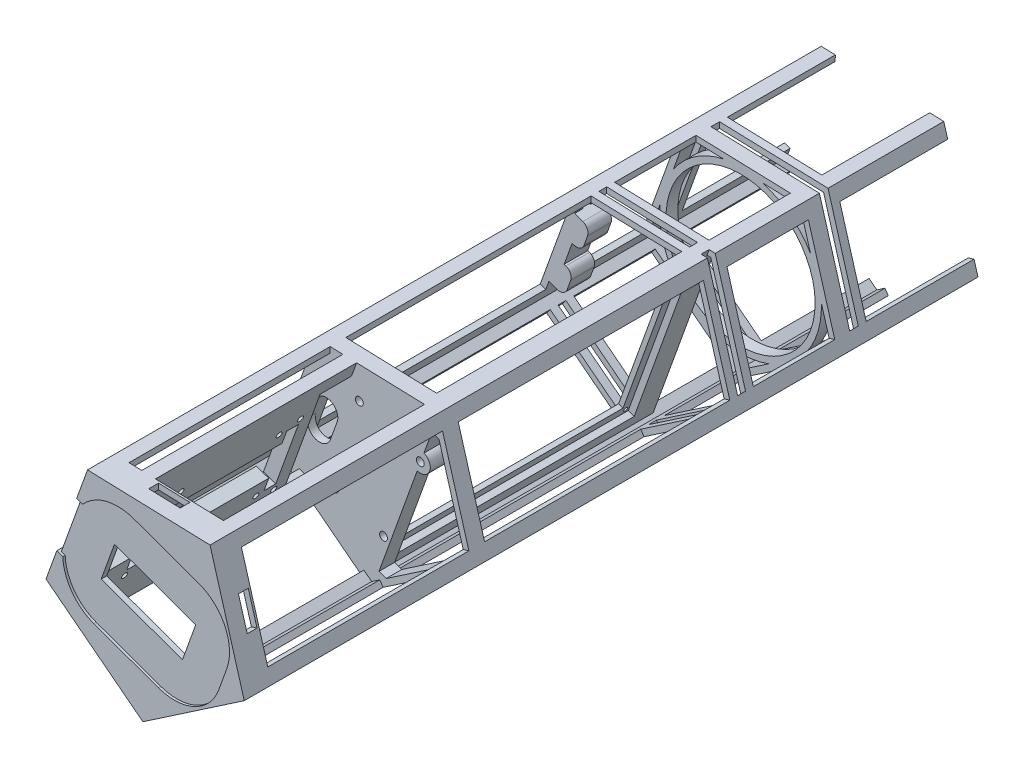
SolidWorks part; units mm, degrees
ref_plane "Front Plane" through (0, 0, 0) normal (0, 0, 1) x (1, 0, 0)
ref_plane "Top Plane" through (0, 0, 0) normal (0, 1, 0) x (1, 0, 0)
ref_plane "Right Plane" through (0, 0, 0) normal (1, 0, 0) x (0, 0, -1)
sketch "Sketch3" plane through (0, 0, 0) normal (0, 0, 1) x (1, 0, 0)
  line L0 (0, 0) -> (16.2851, 21.0012) construction
  line L1 (15.1489, 19.536) -> (-13.8986, 20.4445)
  line L2 (-13.8986, 20.4445) -> (-23.7387, -6.9006)
  line L3 (-23.7387, -6.9006) -> (-0.7728, -24.7093)
  line L4 (-0.7728, -24.7093) -> (23.2611, -8.3705)
  line L5 (0, 0) -> (29.9163, 0) construction
  line L6 (0, 0) -> (25.0057, -8.9983) construction
  line L10 (-0.8307, -26.5625) -> (25.0057, -8.9983)
  line L11 (25.0057, -8.9983) -> (16.2851, 21.0012)
  line L12 (16.2851, 21.0012) -> (-14.941, 21.9778)
  line L13 (-14.941, 21.9778) -> (-25.5191, -7.4182)
  line L14 (-25.5191, -7.4182) -> (-0.8307, -26.5625)
  line L15 (23.2611, -8.3705) -> (15.1489, 19.536)
  circle A0 centre (0, 0) radius 20 construction
  point P4 (0, 0)
  point P14 (0, 0)
  dimension "D2" = 40
extrude "Boss-Extrude2" add sketch "Sketch3" along normal blind 185
ref_plane "Plane1" through (0, 0, 92.5) normal (0, 0, 1) x (1, 0, 0)
sketch "Sketch4" plane through (0, 0, 0) normal (0, 0, -1) x (-1, 0, 0)
  line L0 (14.745, 18.0921) -> (16.1564, 18.6)
  line L1 (13.8986, 20.4445) -> (23.7387, -6.9006) construction
  line L2 (14.941, 21.9778) -> (25.5191, -7.4182) construction
  line L3 (24.3036, -4.0404) -> (22.8922, -4.5483)
  line L4 (22.8922, -4.5483) -> (14.745, 18.0921)
  line L5 (24.3036, -4.0404) -> (16.1564, 18.6)
  dimension "D1" = 2.5
  dimension "D2" = 2.5
extrude "Cut-Extrude1" cut sketch "Sketch4" against normal offset from surface (180 mm away) 5 up to face at (0, 0, 185)
ref_point "Point1"
ref_axis "Axis1" through (0, 0, 185) along (0, 0, 1)
pattern_circular "CirPattern1" count 5 over 360 about axis through (0, 0, 185) along (0, 0, 1) of "Cut-Extrude1"
ref_plane "Plane2" through (0, 0, 92.5) normal (0, 0, 1) x (1, 0, 0)
sketch "Sketch5" plane through (0, 0, 92.5) normal (0, 0, 1) x (1, 0, 0)
  line L0 (-2.0696, -25.6018) -> (14.7182, 21.0502) construction
  line L2 (-24.1133, -8.5083) -> (-1.8275, -25.7895) construction
  line L3 (23.2611, -8.3705) -> (0, 0) construction
  line L4 (-4.3961, -23.7977) -> (11.7756, 21.1422)
  line L8 (-2.0696, -25.6018) -> (-4.3961, -23.7977)
  line L10 (14.7182, 21.0502) -> (11.7756, 21.1422)
  line L11 (-2.0696, -25.6018) -> (14.7182, 21.0502)
  line L12 (-22.8004, 22.2236) -> (6.2471, 21.3151) construction
  dimension "D1" = 18
  dimension "D2" = 2.8
extrude "Boss-Extrude3" add sketch "Sketch5" along normal mid plane 64.5
sketch "Sketch6" plane through (0, 0, 124.75) normal (0, 0, 1) x (1, 0, 0)
  line L5 (-25.5191, -7.4182) -> (-0.8307, -26.5625)
  line L6 (-0.8307, -26.5625) -> (25.0057, -8.9983)
  line L7 (25.0057, -8.9983) -> (16.2851, 21.0012)
  line L8 (16.2851, 21.0012) -> (-14.941, 21.9778)
  line L9 (-14.941, 21.9778) -> (-25.5191, -7.4182)
  line L10 (-25.5191, -7.4182) -> (-0.8307, -26.5625)
  line L11 (-0.8307, -26.5625) -> (25.0057, -8.9983)
  line L12 (25.0057, -8.9983) -> (16.2851, 21.0012)
  line L13 (16.2851, 21.0012) -> (-14.941, 21.9778)
  line L14 (-14.941, 21.9778) -> (-25.5191, -7.4182)
  dimension "D1" = 0
extrude "Boss-Extrude4" add sketch "Sketch6" along normal blind 4
sketch "Sketch7" plane through (0, 0, 124.75) normal (0, 0, -1) x (-1, 0, 0)
  line L0 (-3.6897, -1.3278) -> (20.23, 7.2798) construction
  line L1 (-11.7756, 21.1422) -> (4.3961, -23.7977) construction
  line L2 (16.1564, 18.6) -> (24.3036, -4.0404) construction
  line L4 (19.0326, -2.4504) -> (13.1071, 14.0159)
  line L5 (0.2139, -9.2223) -> (-5.7115, 7.244)
  line L7 (19.0326, -2.4504) -> (-5.7115, 7.244) construction
  line L8 (0.2139, -9.2223) -> (13.1071, 14.0159) construction
  line L9 (9.6232, -5.8364) -> (3.6978, 10.63) construction
  line L11 (-11.7756, 21.1422) -> (4.3961, -23.7977) construction
  arc A0 (-5.7115, 7.244) -> (13.1071, 14.0159) centre (3.6978, 10.63) cw
  arc A1 (0.2139, -9.2223) -> (19.0326, -2.4504) centre (9.6232, -5.8364) ccw
  point P7 (6.6605, 2.3968)
  point P9 (13.0092, -15.2457)
  point P14 (0.3119, 20.0393)
  point P15 (0, 0)
  point P16 (7.1485, 2.5724)
  point P17 (7.4662, 2.6867)
  dimension "D1" = 37.5
  dimension "D2" = 20
  dimension "D3" = 1
extrude "Cut-Extrude2" cut sketch "Sketch7" against normal blind 2
sketch "Sketch8" plane through (6.3243, -2.2758, 0) normal (0.9409, -0.3386, 0) x (0, 0, -1)
  line L0 (-60.25, 0) -> (-124.75, 0) construction
  line L1 (-124.75, -23.2131) -> (-124.75, 23.2131) construction
  line L3 (-60.25, -23.2131) -> (-60.25, 23.2131) construction
  line L5 (-123, -20.5) -> (-123, 20.5)
  line L6 (-123, -20.5) -> (-62, -20.5)
  line L7 (-123, 20.5) -> (-62, 20.5)
  line L8 (-62, -20.5) -> (-62, 20.5)
  line L14 (-62, 20.5) -> (-123, -20.5) construction
  line L15 (-62, -20.5) -> (-123, 20.5) construction
  point P2 (0, 0)
  point P5 (0, 0)
  point P6 (0, 0)
  point P11 (-92.5, 0)
  point P14 (-92.5, 0)
  dimension "D1" = 61
  dimension "D2" = 41
extrude "Cut-Extrude3" cut sketch "Sketch8" against normal blind 1.6
sketch "Sketch9" plane through (4.8189, -1.7341, 0) normal (0.9409, -0.3386, 0) x (0, 0, -1)
  line L8 (-121, -18.5) -> (-64, -18.5)
  line L9 (-64, -18.5) -> (-64, 18.5)
  line L10 (-64, 18.5) -> (-121, 18.5)
  line L11 (-121, 18.5) -> (-121, -18.5)
  line L12 (-121, -18.5) -> (-64, -18.5)
  line L13 (-64, -18.5) -> (-64, 18.5)
  line L14 (-64, 18.5) -> (-121, 18.5)
  line L15 (-121, 18.5) -> (-121, -18.5)
  dimension "D1" = 2
extrude "Cut-Extrude4" cut sketch "Sketch9" against normal up to surface (1.2 mm away) up to face at (3.6897, -1.3278, 92.5)
sketch "Sketch10" plane through (0, 0, 60.25) normal (0, 0, -1) x (-1, 0, 0)
  line L25 (-23.2611, -8.3705) -> (0.7728, -24.7093)
  line L26 (0.7728, -24.7093) -> (23.7387, -6.9006)
  line L27 (23.7387, -6.9006) -> (13.8986, 20.4445)
  line L28 (13.8986, 20.4445) -> (-15.1489, 19.536)
  line L29 (-15.1489, 19.536) -> (-23.2611, -8.3705)
  line L30 (0.8307, -26.5625) -> (25.5191, -7.4182)
  line L31 (-25.0057, -8.9983) -> (0.8307, -26.5625)
  line L32 (-16.2851, 21.0012) -> (-25.0057, -8.9983)
  line L33 (14.941, 21.9778) -> (-16.2851, 21.0012)
  line L34 (25.5191, -7.4182) -> (14.941, 21.9778)
  line L40 (0.8307, -26.5625) -> (25.5191, -7.4182)
  line L41 (-25.0057, -8.9983) -> (0.8307, -26.5625)
  line L42 (-16.2851, 21.0012) -> (-25.0057, -8.9983)
  line L43 (14.941, 21.9778) -> (-16.2851, 21.0012)
  line L44 (25.5191, -7.4182) -> (14.941, 21.9778)
  point P8 (0, 0)
  point P11 (-0.8687, -22.1155)
  dimension "D1" = 0
extrude "Boss-Extrude5" add sketch "Sketch10" against normal blind 2
sketch "Sketch11" plane through (0, 0, 60.25) normal (0, 0, -1) x (-1, 0, 0)
  line L0 (3.8621, -22.3137) -> (4.3961, -23.7977)
  line L1 (4.3961, -23.7977) -> (3.6676, -24.3627)
  line L2 (-11.2416, 19.6582) -> (-11.7756, 21.1422)
  line L3 (-11.7756, 21.1422) -> (-12.697, 21.1134)
  line L4 (21.7631, -8.4326) -> (3.8621, -22.3137)
  line L7 (3.8621, -22.3137) -> (-11.2416, 19.6582)
  line L9 (-14.1842, 19.5662) -> (1.5355, -24.1178)
  line L10 (-14.1842, 19.5662) -> (1.5355, -24.1178)
  line L11 (-12.697, 21.1134) -> (11.3529, 21.8656) construction
  line L13 (3.8621, -22.3137) -> (-11.2416, 19.6582) construction
  line L18 (22.6823, -9.618) -> (3.6676, -24.3627) construction
  line L19 (3.8621, -22.3137) -> (-11.2416, 19.6582)
  line L27 (-11.2416, 19.6582) -> (11.3998, 20.3663)
  line L31 (1.5355, -24.1178) -> (2.7484, -23.1773)
  line L33 (1.5355, -24.1178) -> (2.7484, -23.1773)
  line L35 (2.7484, -23.1773) -> (3.6676, -24.3627)
  line L37 (2.7484, -23.1773) -> (3.6676, -24.3627)
  line L39 (3.6676, -24.3627) -> (22.6823, -9.618)
  line L41 (22.6823, -9.618) -> (21.7631, -8.4326)
  line L43 (11.3998, 20.3663) -> (11.3529, 21.8656)
  line L45 (11.3529, 21.8656) -> (-12.697, 21.1134)
  line L47 (-12.697, 21.1134) -> (-12.6502, 19.6141)
  line L48 (-12.697, 21.1134) -> (-12.6502, 19.6141)
  line L49 (-12.6502, 19.6141) -> (-14.1842, 19.5662)
  line L50 (-12.6502, 19.6141) -> (-14.1842, 19.5662)
  dimension "D1" = 0
extrude "Boss-Extrude6" add sketch "Sketch11" along normal blind 4
sketch "Sketch12" plane through (0, 0, 56.25) normal (0, 0, -1) x (-1, 0, 0)
  line L0 (0.7728, -24.7093) -> (23.7387, -6.9006)
  line L1 (23.7387, -6.9006) -> (13.8986, 20.4445)
  line L2 (13.8986, 20.4445) -> (-15.1489, 19.536)
  line L3 (-15.1489, 19.536) -> (-23.2611, -8.3705)
  line L4 (-23.2611, -8.3705) -> (0.7728, -24.7093)
  line L5 (0.8307, -26.5625) -> (25.5191, -7.4182)
  line L6 (-25.0057, -8.9983) -> (0.8307, -26.5625)
  line L7 (-16.2851, 21.0012) -> (-25.0057, -8.9983)
  line L8 (14.941, 21.9778) -> (-16.2851, 21.0012)
  line L9 (25.5191, -7.4182) -> (14.941, 21.9778)
  line L10 (0.8307, -26.5625) -> (25.5191, -7.4182)
  line L11 (-25.0057, -8.9983) -> (0.8307, -26.5625)
  line L12 (-16.2851, 21.0012) -> (-25.0057, -8.9983)
  line L13 (14.941, 21.9778) -> (-16.2851, 21.0012)
  line L14 (25.5191, -7.4182) -> (14.941, 21.9778)
  point P15 (0, -21.7043)
  dimension "D1" = 0
extrude "Boss-Extrude7" add sketch "Sketch12" against normal blind 2
ref_plane "Plane3" through (0, 0, 32.5) normal (0, 0, 1) x (1, 0, 0)
sketch "Sketch14" plane through (0, 0, 32.5) normal (0, 0, 1) x (1, 0, 0)
  line L5 (-25.5191, -7.4182) -> (-0.8307, -26.5625)
  line L6 (-0.8307, -26.5625) -> (25.0057, -8.9983)
  line L7 (25.0057, -8.9983) -> (16.2851, 21.0012)
  line L8 (16.2851, 21.0012) -> (-14.941, 21.9778)
  line L9 (-14.941, 21.9778) -> (-25.5191, -7.4182)
  line L11 (-0.8307, -26.5625) -> (25.0057, -8.9983)
  line L12 (25.0057, -8.9983) -> (16.2851, 21.0012)
  line L16 (23.2611, -8.3705) -> (15.3259, -13.7651)
  line L18 (-0.7728, -24.7093) -> (-8.3554, -18.8294)
  line L20 (-23.7387, -6.9006) -> (-20.4898, 2.1279)
  line L22 (-13.8986, 20.4445) -> (-4.308, 20.1445)
  line L24 (15.1489, 19.536) -> (17.8273, 10.3221)
  line L25 (7.1625, -19.3147) -> (-0.7728, -24.7093)
  line L26 (20.5827, 0.8433) -> (23.2611, -8.3705)
  line L27 (5.5584, 19.8359) -> (15.1489, 19.536)
  line L28 (-17.1475, 11.416) -> (-13.8986, 20.4445)
  line L29 (-16.1561, -12.7805) -> (-23.7387, -6.9006)
  line L30 (16.2851, 21.0012) -> (-14.941, 21.9778)
  line L31 (-14.941, 21.9778) -> (-25.5191, -7.4182)
  line L32 (-25.5191, -7.4182) -> (-0.8307, -26.5625)
  circle A3 centre (0, 0) radius 19
  arc A8 (15.3259, -13.7651) -> (20.5827, 0.8433) centre (0, 0) ccw
  circle A9 centre (0, 0) radius 20.6 construction
  arc A10 (17.8273, 10.3221) -> (5.5584, 19.8359) centre (0, 0) ccw
  arc A11 (-4.308, 20.1445) -> (-17.1475, 11.416) centre (0, 0) ccw
  arc A12 (-20.4898, 2.1279) -> (-16.1561, -12.7805) centre (0, 0) ccw
  arc A13 (-8.3554, -18.8294) -> (7.1625, -19.3147) centre (0, 0) ccw
  dimension "D2" = 38
  dimension "D1" = 0
  dimension "D3" = 1.6
extrude "Boss-Extrude8" add sketch "Sketch14" along normal blind 3
ref_plane "Plane4" through (0, 0, 29.5) normal (0, 0, -1) x (-1, 0, 0)
sketch "Sketch15" plane through (0, 0, 29.5) normal (0, 0, -1) x (-1, 0, 0)
  line L0 (-23.2611, -8.3705) -> (0.7728, -24.7093)
  line L1 (0.7728, -24.7093) -> (23.7387, -6.9006)
  line L2 (23.7387, -6.9006) -> (13.8986, 20.4445)
  line L3 (13.8986, 20.4445) -> (-15.1489, 19.536)
  line L4 (-15.1489, 19.536) -> (-23.2611, -8.3705)
  line L5 (0.8307, -26.5625) -> (25.5191, -7.4182)
  line L6 (-25.0057, -8.9983) -> (0.8307, -26.5625)
  line L7 (-16.2851, 21.0012) -> (-25.0057, -8.9983)
  line L8 (14.941, 21.9778) -> (-16.2851, 21.0012)
  line L9 (25.5191, -7.4182) -> (14.941, 21.9778)
  line L10 (0.8307, -26.5625) -> (25.5191, -7.4182)
  line L11 (-25.0057, -8.9983) -> (0.8307, -26.5625)
  line L12 (-16.2851, 21.0012) -> (-25.0057, -8.9983)
  line L13 (14.941, 21.9778) -> (-16.2851, 21.0012)
  line L14 (25.5191, -7.4182) -> (14.941, 21.9778)
  point P15 (-13.7443, 17.3013)
  point P16 (-15.1489, 19.536)
  dimension "D1" = 0
extrude "Boss-Extrude9" add sketch "Sketch15" along normal blind 2
sketch "Sketch18" plane through (0, 0, 32.5) normal (0, 0, -1) x (-1, 0, 0)
  line L0 (22.8922, -4.5483) -> (24.3036, -4.0404)
  line L1 (24.3036, -4.0404) -> (16.1564, 18.6)
  line L2 (16.1564, 18.6) -> (14.745, 18.0921)
  line L3 (14.745, 18.0921) -> (22.8922, -4.5483)
  line L4 (11.3998, 20.3663) -> (11.3529, 21.8656)
  line L5 (11.3529, 21.8656) -> (-12.697, 21.1134)
  line L6 (-12.697, 21.1134) -> (-12.6502, 19.6141)
  line L7 (-12.6502, 19.6141) -> (11.3998, 20.3663)
  line L8 (-15.8468, 17.1354) -> (-17.2872, 17.5541)
  line L9 (-17.2872, 17.5541) -> (-24.0037, -5.5512)
  line L10 (-24.0037, -5.5512) -> (-22.5633, -5.9699)
  line L11 (-22.5633, -5.9699) -> (-15.8468, 17.1354)
  line L12 (-21.1936, -9.7761) -> (-22.0369, -11.0166)
  line L13 (-22.0369, -11.0166) -> (-2.138, -24.5443)
  line L14 (-2.138, -24.5443) -> (-1.2947, -23.3038)
  line L15 (-1.2947, -23.3038) -> (-21.1936, -9.7761)
  line L16 (3.6676, -24.3627) -> (22.6823, -9.618)
  line L17 (22.6823, -9.618) -> (21.7631, -8.4326)
  line L18 (21.7631, -8.4326) -> (2.7484, -23.1773)
  line L19 (2.7484, -23.1773) -> (3.6676, -24.3627)
extrude "Boss-Extrude10" add sketch "Sketch18" along normal blind 0.8
sketch "Sketch25" plane through (0, 0, 56.25) normal (0, 0, -1) x (-1, 0, 0)
  line L0 (23.5979, -4.2944) -> (15.4507, 18.3461) construction
  line L1 (15.0407, 12.1611) -> (19.3409, 0.2112) construction
  line L2 (16.24, 16.1529) -> (11.5729, 14.4735)
  line L3 (24.3036, -4.0404) -> (22.8922, -4.5483) construction
  line L8 (14.745, 18.0921) -> (16.1564, 18.6) construction
  line L9 (22.5345, -1.339) -> (16.5142, 15.3907) construction
  line L10 (22.5345, -1.339) -> (4.6097, -7.7893) construction
  line L11 (16.5142, 15.3907) -> (-1.4105, 8.9405) construction
  line L12 (4.6097, -7.7893) -> (-1.4105, 8.9405) construction
  line L13 (19.5243, 7.0259) -> (0, 0) construction
  line L14 (16.24, 16.1529) -> (18.5086, 9.8487) construction
  line L15 (11.5729, 14.4735) -> (13.8415, 8.1692)
  line L16 (16.175, 9.0089) -> (13.8415, 8.1692)
  line L17 (13.9065, 15.3132) -> (16.175, 9.0089) construction
  line L18 (17.3743, 13.0008) -> (12.7072, 11.3213) construction
  line L19 (21.6744, 1.0509) -> (17.0074, -0.6285) construction
  line L20 (20.4752, -2.9409) -> (18.2066, 3.3633) construction
  line L21 (18.2066, 3.3633) -> (15.8731, 2.5236)
  line L22 (18.1417, -3.7806) -> (15.8731, 2.5236)
  line L23 (22.8087, -2.1012) -> (20.5401, 4.2031) construction
  line L24 (22.8087, -2.1012) -> (18.1417, -3.7806)
  line L25 (18.5086, 9.8487) -> (20.5401, 4.2031) construction
  line L28 (16.175, 9.0089) -> (18.2066, 3.3633)
  line L29 (16.24, 16.1529) -> (16.9457, 16.4068)
  line L30 (24.3036, -4.0404) -> (16.1564, 18.6) construction
  line L31 (16.9457, 16.4068) -> (23.5144, -1.8472)
  line L32 (23.5144, -1.8472) -> (22.8087, -2.1012)
  circle A0 centre (15.0407, 12.1611) radius 1 construction
  circle A1 centre (19.3409, 0.2112) radius 1 construction
  circle A2 centre (19.3409, 0.2112) radius 1 construction
  point P17 (17.1908, 6.1861)
  dimension "D3" = 2
  dimension "D4" = 12.7
  dimension "D1" = 17.78
  dimension "D2" = 19.05
  dimension "D5" = 16.57
  dimension "D6" = 6
sketch "Sketch26" plane through (0, 0, 56.25) normal (0, 0, -1) x (-1, 0, 0)
  circle A0 centre (19.3409, 0.2112) radius 1 construction
  circle A1 centre (19.3409, 0.2112) radius 1
  circle A2 centre (15.0407, 12.1611) radius 1 construction
  circle A3 centre (15.0407, 12.1611) radius 1
sketch "Sketch28" plane through (0, 0, 56.25) normal (0, 0, -1) x (-1, 0, 0)
  line L0 (23.5979, -4.2944) -> (15.4507, 18.3461) construction
  line L1 (22.5345, -1.339) -> (4.6097, -7.7893) construction
  line L2 (4.6097, -7.7893) -> (-1.4105, 8.9405) construction
  line L3 (16.5142, 15.3907) -> (-1.4105, 8.9405) construction
  line L4 (22.5345, -1.339) -> (16.5142, 15.3907) construction
  line L5 (22.5345, -1.339) -> (4.6097, -7.7893) construction
  line L6 (4.6097, -7.7893) -> (-1.4105, 8.9405) construction
  line L7 (16.5142, 15.3907) -> (-1.4105, 8.9405) construction
  line L8 (22.7904, -1.4595) -> (16.6347, 15.6466)
  line L9 (16.6347, 15.6466) -> (-1.6664, 9.061)
  line L10 (4.4892, -8.0452) -> (-1.6664, 9.061)
  line L11 (22.7904, -1.4595) -> (4.4892, -8.0452)
  dimension "D1" = 0.2
extrude "Boss-Extrude12" add sketch "Sketch25" against normal up to surface (6 mm away) up to face at (-19.5243, 7.0259, 62.25)
extrude "Cut-Extrude6" cut sketch "Sketch26" against normal blind 5
fillet "Fillet1" radius 2 4 edges at (-18.1417, -3.7806, 59.25) (-15.8731, 2.5236, 59.25) (-13.8415, 8.1692, 59.25) (-11.5729, 14.4735, 59.25)
sketch "Sketch29" plane through (0, 0, 185) normal (0, 0, 1) x (1, 0, 0)
  line L5 (-25.5191, -7.4182) -> (-0.8307, -26.5625)
  line L6 (-0.8307, -26.5625) -> (25.0057, -8.9983)
  line L7 (25.0057, -8.9983) -> (16.2851, 21.0012)
  line L8 (16.2851, 21.0012) -> (-14.941, 21.9778)
  line L9 (-14.941, 21.9778) -> (-25.5191, -7.4182)
  line L10 (-25.5191, -7.4182) -> (-0.8307, -26.5625)
  line L11 (-0.8307, -26.5625) -> (25.0057, -8.9983)
  line L12 (25.0057, -8.9983) -> (16.2851, 21.0012)
  line L13 (16.2851, 21.0012) -> (-14.941, 21.9778)
  line L14 (-14.941, 21.9778) -> (-25.5191, -7.4182)
  dimension "D1" = 0
extrude "Boss-Extrude13" add sketch "Sketch29" along normal blind 2
sketch "Sketch30" plane through (0, 0, 187) normal (0, 0, 1) x (1, 0, 0)
  line L0 (25.0057, -8.9983) -> (-20.23, 7.2798) construction
  line L1 (-14.941, 21.9778) -> (-25.5191, -7.4182) construction
  line L2 (3.1542, -17.0767) -> (-13.3121, -11.1513)
  line L3 (18.5086, -9.8487) -> (20.5401, -4.2031)
  line L4 (-20.5401, 4.2031) -> (-18.5086, 9.8487)
  line L5 (13.3121, 11.1513) -> (-3.1542, 17.0767)
  line L6 (14.4454, -21.1398) -> (-14.4454, 21.1398) construction
  line L7 (-24.6033, -7.0881) -> (24.6033, 7.0881) construction
  line L8 (19.5243, -7.0259) -> (-19.5243, 7.0259) construction
  arc A0 (18.5086, -9.8487) -> (3.1542, -17.0767) centre (7.2174, -5.7855) cw
  arc A1 (-18.5086, 9.8487) -> (-3.1542, 17.0767) centre (-7.2174, 5.7855) cw
  arc A2 (-13.3121, -11.1513) -> (-20.5401, 4.2031) centre (-9.2489, 0.1399) cw
  arc A3 (20.5401, -4.2031) -> (13.3121, 11.1513) centre (9.2489, -0.1399) ccw
  point P4 (0, 0)
  point P5 (0, 0)
  point P26 (0, 0)
  dimension "D3" = 12
  dimension "D1" = 30
  dimension "D2" = 41.5
extrude "Cut-Extrude8" cut sketch "Sketch30" against normal blind 0.6
sketch "Sketch31" plane through (0, 0, 186.4) normal (0, 0, 1) x (1, 0, 0)
  line L0 (25.0057, -8.9983) -> (0, 0) construction
  line L1 (12.0432, 0.9801) -> (8.6573, -8.4292)
  line L2 (12.0432, 0.9801) -> (-8.6573, 8.4292)
  line L3 (8.6573, -8.4292) -> (-12.0432, -0.9801)
  line L4 (-8.6573, 8.4292) -> (-12.0432, -0.9801)
  line L5 (12.0432, 0.9801) -> (-12.0432, -0.9801) construction
  line L6 (8.6573, -8.4292) -> (-8.6573, 8.4292) construction
  line L7 (-10.3503, 3.7246) -> (10.3503, -3.7246) construction
  dimension "D1" = 22
  dimension "D2" = 10
extrude "Cut-Extrude9" cut sketch "Sketch31" against normal up to surface (1.4 mm away) up to face at (0, 0, 185)
sketch "Sketch32" plane through (0, 0, 187) normal (0, 0, 1) x (1, 0, 0)
  line L0 (0, 0) -> (-36.3954, 13.0969) construction
  line L1 (-22.7695, 0.2228) -> (-21.2398, -0.3276)
  line L3 (-14.941, 21.9778) -> (-25.5191, -7.4182) construction
  line L4 (-17.6906, 14.3368) -> (-16.1609, 13.7863)
  line L5 (-18.5086, 9.8487) -> (-20.5401, 4.2031) construction
  line L6 (-18.5086, 9.8487) -> (-20.5401, 4.2031)
  line L7 (-17.6906, 14.3368) -> (-22.7695, 0.2228)
  arc A0 (-20.5401, 4.2031) -> (-13.3121, -11.1513) centre (-9.2489, 0.1399) ccw construction
  arc A1 (-20.5401, 4.2031) -> (-13.3121, -11.1513) centre (-9.2489, 0.1399) ccw construction
  arc A3 (-3.1542, 17.0767) -> (-18.5086, 9.8487) centre (-7.2174, 5.7855) ccw construction
  arc A4 (-16.1609, 13.7863) -> (-18.5086, 9.8487) centre (-7.2174, 5.7855) ccw
  arc A5 (-20.5401, 4.2031) -> (-21.2398, -0.3276) centre (-9.2489, 0.1399) ccw
  point P5 (0, 0)
  dimension "D1" = 7.5
extrude "Cut-Extrude11" cut sketch "Sketch32" against normal up to surface (0.6 mm away) up to face at (0, 0, 186.4)
sketch "Sketch34" plane through (0, 0, 186.4) normal (0, 0, 1) x (1, 0, 0)
  line L0 (-22.7695, 0.2228) -> (-17.6906, 14.3368)
  line L1 (-22.7695, 0.2228) -> (-22.0638, -0.0311)
  line L2 (-17.6906, 14.3368) -> (-16.9849, 14.0828)
  line L3 (-22.0638, -0.0311) -> (-16.9849, 14.0828)
  line L4 (-13.3121, -11.1513) -> (3.1542, -17.0767)
  line L5 (18.5086, -9.8487) -> (20.5401, -4.2031)
  line L6 (13.3121, 11.1513) -> (-3.1542, 17.0767)
  line L7 (-18.5086, 9.8487) -> (-20.5401, 4.2031)
  line L8 (-13.3121, -11.1513) -> (3.1542, -17.0767) construction
  line L9 (18.5086, -9.8487) -> (20.5401, -4.2031) construction
  line L10 (13.3121, 11.1513) -> (-3.1542, 17.0767) construction
  line L11 (-18.5086, 9.8487) -> (-20.5401, 4.2031) construction
  arc A4 (3.1542, -17.0767) -> (18.5086, -9.8487) centre (7.2174, -5.7855) ccw
  arc A5 (20.5401, -4.2031) -> (13.3121, 11.1513) centre (9.2489, -0.1399) ccw
  arc A6 (-3.1542, 17.0767) -> (-18.5086, 9.8487) centre (-7.2174, 5.7855) ccw
  arc A7 (-20.5401, 4.2031) -> (-13.3121, -11.1513) centre (-9.2489, 0.1399) ccw
  arc A8 (3.1542, -17.0767) -> (18.5086, -9.8487) centre (7.2174, -5.7855) ccw construction
  arc A9 (20.5401, -4.2031) -> (13.3121, 11.1513) centre (9.2489, -0.1399) ccw construction
  arc A10 (-3.1542, 17.0767) -> (-18.5086, 9.8487) centre (-7.2174, 5.7855) ccw construction
  arc A11 (-20.5401, 4.2031) -> (-13.3121, -11.1513) centre (-9.2489, 0.1399) ccw construction
  dimension "D1" = 0
sketch "Sketch38" plane through (0, 0, 124.75) normal (0, 0, -1) x (-1, 0, 0)
  line L5 (13.8986, 20.4445) -> (-15.1489, 19.536)
  line L6 (-15.1489, 19.536) -> (-23.2611, -8.3705)
  line L7 (-23.2611, -8.3705) -> (0.7728, -24.7093)
  line L8 (0.7728, -24.7093) -> (23.7387, -6.9006)
  line L9 (23.7387, -6.9006) -> (13.8986, 20.4445)
  line L11 (-16.3988, 15.2363) -> (-23.2611, -8.3705)
  line L12 (-23.2611, -8.3705) -> (-2.9303, -22.1919)
  line L16 (-1.0956, -21.5316) -> (-2.9303, -22.1919)
  line L17 (0.03, -24.6596) -> (-15.6897, 19.0244)
  line L18 (-1.0956, -21.5316) -> (-14.5641, 15.8965)
  line L19 (-14.5641, 15.8965) -> (-16.3988, 15.2363)
  dimension "D3" = 1.6
  dimension "D4" = 1.6
  dimension "D1" = 0
  dimension "D2" = 1.6
extrude "Cut-Extrude14" cut sketch "Sketch38" against normal up to surface (4 mm away) up to face at (0, 0, 128.75)
sketch "Sketch40" plane through (-18.8186, 6.7719, 0) normal (0.9409, -0.3386, 0) x (0, 0, -1)
  line L0 (-185, 14.5309) -> (-185, -14.5309) construction
  line L1 (-185, 7.5) -> (-183.5, 7.5)
  line L2 (-185, 7.5) -> (-185, -7.5)
  line L3 (-185, -7.5) -> (-183.5, -7.5)
  line L4 (-183.5, 7.5) -> (-183.5, -7.5)
  line L5 (-183.5, 0) -> (-185, 0) construction
  point P8 (-185, -11.8004)
  point P9 (-185, 0)
  dimension "D1" = 15
  dimension "D2" = 1.5
extrude "Cut-Extrude15" cut sketch "Sketch40" against normal up to surface (1.5 mm away) up to face at (-23.909, -2.9438, 59.25)
sketch "Sketch41" plane through (-20.23, 7.2798, 0) normal (-0.9409, 0.3386, 0) x (0, 0, 1)
  line L0 (185, -7.5) -> (186.4, -7.5)
  line L1 (185, 7.5) -> (186.4, 7.5)
  line L2 (185, -7.5) -> (185, 7.5)
  line L3 (186.4, 7.5) -> (186.4, -7.5)
extrude "Cut-Extrude16" cut sketch "Sketch41" against normal blind 0.6
ref_plane "Plane5" through (14.5641, 15.8965, 124.75) normal (0.3386, 0.9409, 0) x (0.9409, -0.3386, 0)
sketch "Sketch42" plane through (0, 0, 128.75) normal (0, 0, 1) x (1, 0, 0)
  line L0 (-20.23, 7.2798) -> (0, 0) construction
  line L1 (-16.1564, 18.6) -> (-24.3036, -4.0404) construction
  line L2 (5.4365, -16.774) -> (-14.8782, -9.4637) construction
  line L3 (5.4365, -16.774) -> (14.8782, 9.4637) construction
  line L4 (-14.8782, -9.4637) -> (-5.4365, 16.774) construction
  line L5 (14.8782, 9.4637) -> (-5.4365, 16.774) construction
  line L6 (5.4365, -16.774) -> (-5.4365, 16.774) construction
  line L7 (-14.8782, -9.4637) -> (14.8782, 9.4637) construction
  line L8 (-3.9066, 13.524) -> (11.6282, 7.9338) construction
  line L9 (4.7208, 13.1189) -> (-4.7208, -13.1189) construction
  line L10 (2.2472, -13.2032) -> (-10.1449, -8.7439) construction
  line L11 (-1.5355, -24.1178) -> (14.1842, 19.5662) construction
  line L12 (-1.5355, -24.1178) -> (14.1842, 19.5662)
  line L13 (12.891, 3.9416) -> (6.1392, -14.8212) construction
  line L14 (12.891, 3.9416) -> (10.6328, 4.7542) construction
  line L15 (6.1392, -14.8212) -> (3.881, -14.0086) construction
  line L16 (10.6328, 4.7542) -> (3.881, -14.0086) construction
  circle A0 centre (11.6282, 7.9338) radius 1
  circle A1 centre (-3.9066, 13.524) radius 1
  circle A2 centre (2.2472, -13.2032) radius 1
  circle A3 centre (-10.1449, -8.7439) radius 1
  point P1 (3.8608, 10.7289)
  point P2 (0, 0)
  point P19 (-3.9488, -10.9735)
  point P22 (-0.365, 0)
  point P23 (0, 0)
  point P24 (0, 0)
  point P25 (0, 0)
  dimension "D4" = 2
  dimension "D7" = 2
  dimension "D1" = 21.59
  dimension "D2" = 27.8848
  dimension "D3" = 16.51
  dimension "D5" = 2.54
  dimension "D6" = 13.17
  dimension "D8" = 2.28
  dimension "D9" = 2.4
sketch "Sketch43" plane through (0, 0, 128.75) normal (0, 0, 1) x (1, 0, 0)
  line L1 (10.8306, 5.5214) -> (12.5507, 10.3013)
  line L2 (12.891, 3.9416) -> (10.6328, 4.7542) construction
  line L3 (12.891, 3.9416) -> (10.6328, 4.7542)
  line L4 (1.0956, -21.5316) -> (14.5641, 15.8965) construction
  arc A0 (12.5507, 10.3013) -> (10.8306, 5.5214) centre (11.6282, 7.9338) cw
  point P4 (12.5507, 10.3013)
  line M27 (1.0956, -21.5316) -> (14.5641, 15.8965)
  dimension "D1" = 2.5409
extrude "Boss-Extrude15" add sketch "Sketch43" against normal up to surface (4 mm away) contours A0 M27 region at (12.6767, 7.5565, 128.75) up to face at (11.7736, -4.2367, 124.75)
sketch "Sketch44" plane through (0, 0, 128.75) normal (0, 0, 1) x (1, 0, 0)
  circle A0 centre (-10.1449, -8.7439) radius 1 construction
  circle A1 centre (-3.9066, 13.524) radius 1 construction
  circle A2 centre (-10.1449, -8.7439) radius 1
  circle A3 centre (-3.9066, 13.524) radius 1
extrude "Cut-Extrude18" cut sketch "Sketch42" against normal blind 3.5 contours A0 | A2
extrude "Cut-Extrude19" cut sketch "Sketch44" against normal blind 1.5
sketch "Sketch45" plane through (0, 0, 128.75) normal (0, 0, 1) x (1, 0, 0)
  line L0 (-2.5743, -18.735) -> (9.9537, 16.0795) construction
  line L1 (-2.5743, -18.735) -> (9.9537, 16.0795) construction
  line L2 (13.2655, 17.0133) -> (-0.6169, -21.5649) construction
  line L3 (13.2655, 17.0133) -> (-0.6169, -21.5649) construction
  line L4 (-4.3961, -23.7977) -> (11.7756, 21.1422)
  line L5 (11.7756, 21.1422) -> (14.7182, 21.0502)
  line L6 (14.7182, 21.0502) -> (-2.0696, -25.6018)
  line L7 (-2.0696, -25.6018) -> (-4.3961, -23.7977)
  line L8 (-22.6823, -9.618) -> (-3.6676, -24.3627) construction
  line L11 (12.697, 21.1134) -> (-11.3529, 21.8656) construction
  point P12 (-4.2075, -23.2737)
  point P15 (-1.7497, -24.7131)
  point P16 (0, 0)
  point P17 (0, 0)
  point P18 (-2.366, -26.4257)
  point P19 (15.1057, 22.127)
  point P20 (0, 0)
  point P21 (0, 0)
  point P24 (0, 0)
sketch "Sketch46" plane through (0, 0, 128.75) normal (0, 0, 1) x (1, 0, 0)
  line L0 (-8.1098, 21.7641) -> (-20.1403, -11.5891)
  line L1 (-8.1098, 21.7641) -> (-4.6098, 21.6547)
  line L2 (-20.1403, -11.5891) -> (-17.3745, -13.7339)
  line L3 (-4.6098, 21.6547) -> (-17.3745, -13.7339)
  line L4 (-16.1564, 18.6) -> (-24.3036, -4.0404) construction
  line L5 (-1.5355, -24.1178) -> (14.1842, 19.5662) construction
  line L6 (-1.5355, -24.1178) -> (14.1842, 19.5662)
  line L8 (12.697, 21.1134) -> (-11.3529, 21.8656) construction
  line L9 (-22.6823, -9.618) -> (-3.6676, -24.3627) construction
  point P0 (-7.3249, 21.7396)
  point P8 (0, 0)
  point P9 (-19.9475, -4.0064)
  point P10 (-12.1531, -6.2326)
  point P11 (-12.3147, -6.2275)
  point P12 (-9.5058, -5.2465)
  point P13 (-12.9597, -6.0979)
  point P14 (-10.4429, -7.1862)
  point P15 (-20.0994, -4.5552)
  point P16 (-18.0763, -4.8566)
  point P17 (-21.0837, -4.4729)
  point P20 (-24.6088, -8.1241)
  point P21 (-14.5133, 22.0739)
  point P22 (-14.5167, 22.074)
  line M13 (12.697, 21.1134) -> (-11.3529, 21.8656)
  line M23 (-22.6823, -9.618) -> (-3.6676, -24.3627)
  dimension "D1" = 3.5
  dimension "D2" = 3.5
  dimension "D3" = 6.5
extrude "Boss-Extrude17" add sketch "Sketch46" along normal up to surface (56.25 mm away) contours L3 L0 M13 M23 region at (-12.5431, 4.5184, 128.75) up to face at (-8.552, 3.0775, 185)
sketch "Sketch48" plane through (-14.1227, 5.0941, 0) normal (-0.9407, 0.3393, 0) x (0, 0, 1)
  line L0 (128.75, 18.8059) -> (128.75, -18.8143) construction
  line L1 (128.75, -15) -> (136.75, -15)
  line L2 (128.75, -15) -> (128.75, 15)
  line L3 (128.75, 15) -> (136.75, 15)
  line L4 (136.75, -15) -> (136.75, 15)
  line L5 (128.75, -15) -> (136.75, 15) construction
  line L6 (128.75, 15) -> (136.75, -15) construction
  line L7 (-3.5596, 0) -> (269.0596, 0) construction
  point P0 (132.75, 0)
  point P5 (0, 0)
  dimension "D1" = 8
  dimension "D2" = 30
extrude "Cut-Extrude20" cut sketch "Sketch48" against normal up to surface (3.3295 mm away) up to face at (-10.9922, 3.9602, 168.4375)
sketch "Sketch49" plane through (0, 0, 126.75) normal (0, 0, -1) x (-1, 0, 0)
  line L0 (-2.7488, -0.9892) -> (16.0698, 5.7828) construction
  line L1 (-5.7115, 7.244) -> (0.2139, -9.2223) construction
  line L2 (19.0326, -2.4504) -> (13.1071, 14.0159) construction
  line L3 (12.4006, 7.1193) -> (14.0935, 2.4146) construction
  line L4 (15.2234, 8.1351) -> (16.9163, 3.4304)
  line L5 (9.5778, 6.1035) -> (11.2707, 1.3988)
  arc A0 (15.2234, 8.1351) -> (9.5778, 6.1035) centre (12.4006, 7.1193) ccw
  arc A1 (11.2707, 1.3988) -> (16.9163, 3.4304) centre (14.0935, 2.4146) ccw
  point P8 (13.247, 4.767)
  point P13 (9.2559, 3.3307)
  point P16 (0, 0)
  dimension "D1" = 6
  dimension "D2" = 5
extrude "Cut-Extrude21" cut sketch "Sketch49" against normal up to surface (10 mm away) up to face at (-12.5567, 4.5292, 136.75)
sketch "Sketch50" plane through (-14.1227, 5.0941, 0) normal (-0.9407, 0.3393, 0) x (0, 0, 1)
  line L0 (136.75, 0) -> (181.403, 0) construction
  line L1 (138.0765, -12.1) -> (180.0765, -12.1) construction
  line L2 (138.0765, -12.1) -> (138.0765, 12.1) construction
  line L3 (138.0765, 12.1) -> (180.0765, 12.1) construction
  line L4 (180.0765, -12.1) -> (180.0765, 12.1) construction
  line L5 (138.0765, -12.1) -> (180.0765, 12.1) construction
  line L6 (138.0765, 12.1) -> (180.0765, -12.1) construction
  line L7 (136.75, -15) -> (136.75, 15) construction
  line L8 (159.0765, 12.1) -> (159.0765, -12.1) construction
  circle A0 centre (178.0765, -10.1) radius 0.75
  circle A1 centre (178.0765, 10.1) radius 0.75
  circle A2 centre (140.0765, -10.1) radius 0.75
  circle A3 centre (140.0765, 10.1) radius 0.75
  point P0 (159.0765, 0)
  point P5 (178.0765, -10.85)
  point P6 (178.8265, -10.1)
  dimension "D3" = 1.5
  dimension "D4" = 1.25
  dimension "D1" = 24.2
  dimension "D2" = 42
  dimension "D5" = 1.25
extrude "Cut-Extrude22" cut sketch "Sketch50" against normal up to surface (3.3295 mm away) up to face at (-10.9917, 3.9616, 156.5417)
sketch "Sketch51" plane through (-14.1227, 5.0941, 0) normal (-0.9407, 0.3393, 0) x (0, 0, 1)
  line L0 (180, 0) -> (103.153, 0) construction
  line L1 (143.0765, -8.5) -> (140.0765, -8.5)
  line L2 (143.0765, -8.5) -> (143.0765, -4.9557)
  line L3 (143.0765, 8.5) -> (140.0765, 8.5)
  line L4 (140.0765, -8.5) -> (140.0765, 8.5)
  line L5 (143.0765, -8.5) -> (140.0765, 8.5) construction
  line L6 (143.0765, 8.5) -> (140.0765, -8.5) construction
  line L7 (180, -12.047) -> (180, 12.0147) construction
  line L8 (140.0765, 10.1) -> (140.0765, -10.1) construction
  line L9 (178.0765, 10.1) -> (178.0765, 5.0443) construction
  line L10 (140.0765, 10.1) -> (178.0765, -10.1) construction
  line L11 (140.0765, -10.1) -> (178.0765, 10.1) construction
  line L12 (159.0765, 10.1) -> (159.0765, -10.1) construction
  line L13 (175.0765, 8.5) -> (178.0765, 8.5)
  line L14 (178.0765, -8.5) -> (178.0765, -4.9557)
  line L15 (175.0765, -8.5) -> (178.0765, -8.5)
  line L16 (175.0765, -8.5) -> (175.0765, -4.9557)
  line L17 (143.0765, 5.0443) -> (175.0765, 5.0443)
  line L20 (143.0765, -4.9557) -> (175.0765, -4.9557)
  line L21 (143.0765, 5.0443) -> (175.0765, -4.9557) construction
  line L22 (175.0765, 5.0443) -> (143.0765, -4.9557) construction
  line L23 (143.0765, 5.0443) -> (143.0765, 8.5)
  line L24 (175.0765, 5.0443) -> (175.0765, 8.5)
  line L25 (178.0765, 5.0443) -> (185, 5.0443)
  line L26 (185, 5.0443) -> (185, -4.9557)
  line L27 (185, -4.9557) -> (178.0765, -4.9557)
  line L28 (178.0765, -4.9557) -> (178.0765, -10.1) construction
  line L29 (178.0765, 5.0443) -> (178.0765, 8.5)
  line L30 (185, 16.1438) -> (185, -16.1585) construction
  point P0 (141.5765, 0)
  point P21 (159.0765, 0)
  point P26 (159.0765, 0.0443)
  point P34 (0, 0)
  dimension "D1" = 17
  dimension "D2" = 10
  dimension "D3" = 3
  dimension "D4" = 3.5443
extrude "Cut-Extrude23" cut sketch "Sketch51" against normal up to surface (3.3295 mm away) up to face at (-7.3093, 14.1707, 178.0765)
sketch "Sketch52" plane through (-10.9907, 3.9644, 0) normal (0.9407, -0.3393, 0) x (0, 0, -1)
  line L0 (-170.0765, 8.75) -> (-170.0765, -8.75) construction
  line L1 (-140.0765, 0) -> (-178.0765, 0) construction
  line L2 (-140.0765, 8.5) -> (-140.0765, -8.5) construction
  line L3 (-178.0765, -8.5) -> (-178.0765, -4.9557) construction
  line L4 (-145.0765, 8.75) -> (-145.0765, -8.75) construction
  circle A0 centre (-170.0765, 8.75) radius 0.75
  circle A1 centre (-170.0765, -8.75) radius 0.75
  circle A2 centre (-145.0765, 8.75) radius 0.75
  circle A3 centre (-145.0765, -8.75) radius 0.75
  point P10 (-170.0765, 0)
  point P11 (0, 0)
  point P16 (-145.0765, 0)
  point P17 (0, 0)
  dimension "D1" = 1.5
  dimension "D2" = 17.5
  dimension "D3" = 8
  dimension "D4" = 25
extrude "Cut-Extrude24" cut sketch "Sketch52" against normal up to surface (3.3295 mm away) up to face at (-14.1191, 5.104, 161.199)
sketch "Sketch53" plane through (-20.23, 7.2798, 0) normal (-0.9409, 0.3386, 0) x (0, 0, 1)
  line L0 (183, -4) -> (180.5, -4)
  line L1 (183, -4) -> (183, 4)
  line L2 (180.5, -4) -> (180.5, 4)
  line L3 (183, 4) -> (180.5, 4)
  line L4 (183, -4) -> (180.5, 4) construction
  line L5 (180.5, -4) -> (183, 4) construction
  line L7 (183.5, 0) -> (180, 0) construction
  line L8 (183.5, 7.5) -> (183.5, -7.5) construction
  line L9 (180, -12.0309) -> (180, 12.0309) construction
  point P1 (181.75, 0)
  point P11 (0, 0)
  point P12 (0, 0)
  point P13 (0, 0)
  dimension "D1" = 2.5
  dimension "D2" = 8
extrude "Cut-Extrude25" cut sketch "Sketch53" against normal up to surface (1.5 mm away) up to face at (-18.8186, 6.7719, 165.1667)
pattern_circular "CirPattern5" count 5 over 360 about axis through (0, 0, 185) along (0, 0, 1) of "Cut-Extrude25"
sketch "Sketch54" plane through (4.8189, -1.7341, 0) normal (0.9409, -0.3386, 0) x (0, 0, -1)
  line L0 (-62, 20.5) -> (-123, 20.5) construction
  line L1 (-123, 20.5) -> (-123, -20.5) construction
  line L2 (-64, 0) -> (-121, 0) construction
  line L3 (-64, -18.5) -> (-64, 18.5) construction
  line L4 (-121, 18.5) -> (-121, -18.5) construction
  line L5 (-92.5, 18.5) -> (-92.5, -18.5) construction
  line L6 (-64, 18.5) -> (-121, 18.5) construction
  line L7 (-121, -18.5) -> (-64, -18.5) construction
  circle A0 centre (-122, 19.5) radius 0.5
  circle A1 centre (-122, -19.5) radius 0.5
  circle A2 centre (-63, -19.5) radius 0.5
  circle A3 centre (-63, 19.5) radius 0.5
  dimension "D1" = 1
  dimension "D2" = 1
  dimension "D3" = 1
extrude "Cut-Extrude26" cut sketch "Sketch54" against normal up to surface (1.2 mm away) up to face at (3.6897, -1.3278, 92.5)
ref_plane "Plane8" through (15.2997, 42.5167, 0) normal (-0.3386, -0.9409, 0) x (-0.9409, 0.3386, 0)
sketch "Sketch56" plane through (15.2997, 42.5167, 0) normal (-0.3386, -0.9409, 0) x (-0.9409, 0.3386, 0)
  line L0 (-6.7214, -124.75) -> (-6.7214, -56.25) construction
  line L1 (-6.7214, -124.75) -> (-6.7214, -31.7) construction
  line L2 (-24.4654, -60.25) -> (-24.4654, -58.25) construction
  line L3 (-24.4654, -60.25) -> (-24.4654, -58.25)
  line L4 (-24.4654, -58.25) -> (-6.7214, -58.25)
  line L5 (-6.7214, -58.25) -> (-6.7214, -60.25)
  line L6 (-6.7214, -60.25) -> (-24.4654, -60.25)
  line L7 (-24.4654, -31.7) -> (-24.4654, -29.5) construction
  line L8 (-24.4654, -31.7) -> (-24.4654, -29.5)
  line L9 (-24.4654, -29.5) -> (-6.7214, -29.5)
  line L11 (-6.7214, -31.7) -> (-24.4654, -31.7)
  line L12 (-4.7982, -31.7) -> (-4.7982, -29.5) construction
  line L13 (-4.7982, -31.7) -> (-4.7982, -29.5)
  line L14 (-6.7214, -29.5) -> (-4.7982, -29.5)
  line L15 (-6.7214, -31.7) -> (-4.7982, -31.7)
  line L16 (-6.7214, -29.5) -> (-6.7214, 997.25) construction
extrude "Cut-Extrude28" cut sketch "Sketch56" along normal up to vertex (48.09 mm away) up to point (22.0369, -11.0166, 60.25)
